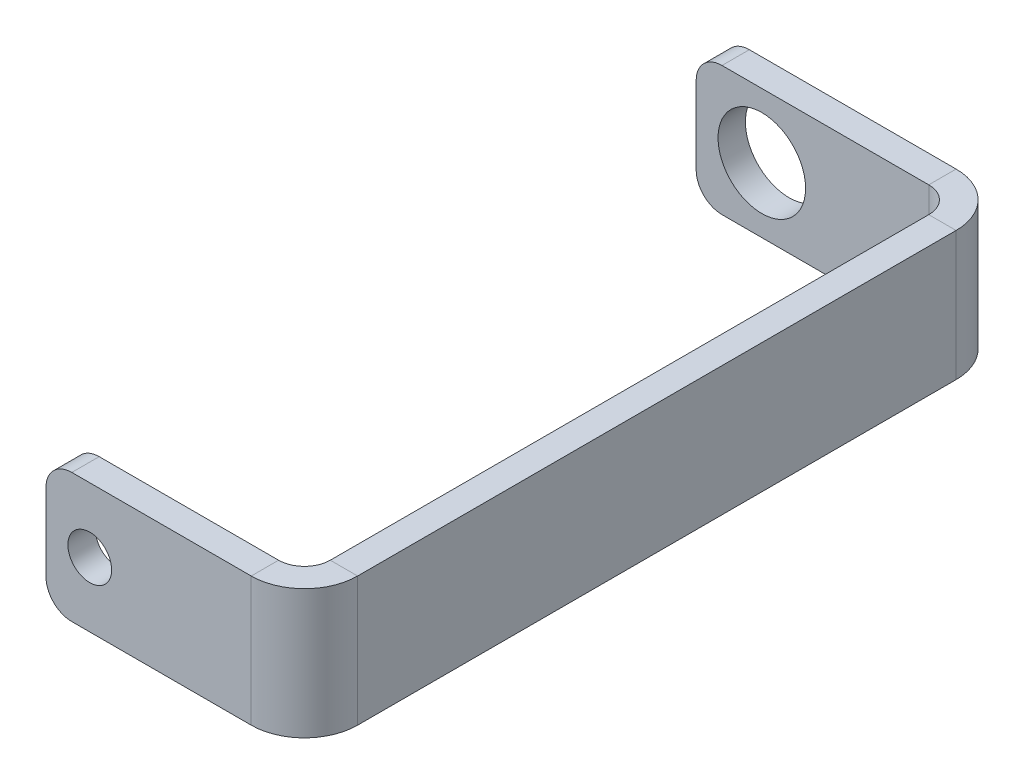
SolidWorks part; units mm, degrees
note: The reader was unsure of these and kept them because the rebuilt part matched: flange length of "Edge-Flange1", "Edge-Flange2".
material "Custom Plastic"
ref_plane "X-Y Datum" through (0, 0, 0) normal (0, 0, 1) x (1, 0, 0)
ref_plane "X-Z Datum" through (0, 0, 0) normal (0, 1, 0) x (1, 0, 0)
ref_plane "Y-Z Datum" through (0, 0, 0) normal (1, 0, 0) x (0, 0, -1)
sketch "Sketch1" plane through (0, 0, 0) normal (0, 0, 1) x (1, 0, 0)
  line L1 (-15, -7.5) -> (15, -7.5)
  line L2 (-15, -7.5) -> (-15, 7.5)
  line L3 (-15, 7.5) -> (15, 7.5)
  line L4 (15, -7.5) -> (15, 7.5)
  line L5 (-15, -7.5) -> (15, 7.5) construction
  line L6 (-15, 7.5) -> (15, -7.5) construction
  point P0 (0, 0)
  dimension "D1" = 30
  dimension "D2" = 15
base flange "Base-Flange1" sketch "Sketch1" thickness 3.175 reverse thickness direction no parameters "D1"=10
edge flange "Edge-Flange1" sketch "Sketch10" flange angle 90 flange length 78.652 flange position material outside bend radius 3 thickness 3.175 relief rectangular parameters "D6"=10
sketch "Sketch10" plane through (15, 0, 0) normal (-1, 0, 0) x (0, -1, 0)
  line L2 (-7.5, 0) -> (-7.5, 75.477)
  line L3 (-7.5, 75.477) -> (7.5, 75.477)
  line L4 (7.5, 75.477) -> (7.5, 0)
  line L5 (7.5, 0) -> (-7.5, 0) construction
  line L6 (7.5, 0) -> (-7.5, 0)
bend "EdgeBend1" bend radius 3 bend angle 90 parameters "D5"=1
edge flange "Edge-Flange2" sketch "Sketch13" flange angle 90 flange length 30 flange position material outside bend radius 3 thickness 3.175 relief rectangular parameters "D6"=10
sketch "Sketch13" plane through (15, 0, 75.477) normal (0, 0, -1) x (0, -1, 0)
  line L2 (-7.5, 0) -> (-7.5, 26.825)
  line L3 (-7.5, 26.825) -> (7.5, 26.825)
  line L4 (7.5, 26.825) -> (7.5, 0)
  line L5 (7.5, 0) -> (-7.5, 0) construction
  line L6 (7.5, 0) -> (-7.5, 0)
bend "EdgeBend2" bend radius 3 bend angle 90 parameters "D5"=2
sketch "Sketch14" plane through (0, 0, 0) normal (0, 0, 1) x (1, 0, 0)
  line L0 (-15, 0) -> (-7.38, 0)
  line L1 (-15, 7.5) -> (-15, -7.5) construction
  circle A0 centre (-7.38, 0) radius 5.08
  dimension "D1" = 10.16
  dimension "D2" = 7.62
extrude "Cut-Extrude1" cut sketch "Sketch14" against normal through all
sketch "Sketch15" plane through (0, 0, 78.652) normal (0, 0, 1) x (1, 0, 0)
  line L0 (-11.825, 0) -> (-6.745, 0)
  line L1 (-11.825, -7.5) -> (-11.825, 7.5) construction
  circle A0 centre (-6.745, 0) radius 2.54
  dimension "D1" = 5.08
extrude "Cut-Extrude2" cut sketch "Sketch15" against normal blind 10
fillet "Fillet1" radius 3 4 edges at (-11.825, 7.5, 77.0645) (-11.825, -7.5, 77.0645) (-15, 7.5, -1.5875) (-15, -7.5, -1.5875)
sketch "Bend-Lines1" [suppressed] plane through (0, 0, 0) normal (0, 1, 0) x (1, 0, 0)
sketch "Bounding-Box1" [suppressed] plane through (0, 0, 0) normal (0, 1, 0) x (1, 0, 0)
sheet metal parameters "Sheet-Metal1" thickness 3.175 parameters "D1"=10
flat pattern "Flat-Pattern1" [suppressed]
sketch "Bend-Lines2" plane through (0, 0, 0) normal (0, 1, 0) x (1, 0, 0)
sketch3d "Bounding-Box2" [suppressed]
  line L0 (-15, -7.5, 0) -> (15, -7.5, 0) construction
  line L1 (-15, 7.5, 0) -> (15, 7.5, 0) construction
  line L2 (-15, -7.5, 0) -> (-15, 7.5, 0) construction
  line L3 (15, -7.5, 0) -> (15, 7.5, 0) construction
sheet metal parameters "Sheet-Metal2" thickness 3.175 parameters "D1"=10
flat pattern "Flat-Pattern1"
sketch "Bend-Lines2" plane through (0, 0, 0) normal (0, 0, 1) x (1, 0, 0)
  line L0 (15.603, -7.5) -> (15.603, 7.5) construction
  line L1 (15.603, -7.5) -> (15.603, 7.5) construction
sketch3d "Bounding-Box2" [suppressed]
  line L0 (-15, -7.5, 0) -> (63.031, -7.5, 0) construction
  line L1 (-15, 7.5, 0) -> (63.031, 7.5, 0) construction
  line L2 (-15, -7.5, 0) -> (-15, 7.5, 0) construction
  line L3 (63.031, -7.5, 0) -> (63.031, 7.5, 0) construction
bend of the flat pattern "Flatten-<EdgeBend1>1"
sheet metal parameters "Sheet-Metal3" thickness 3.175 parameters "D1"=10
flat pattern "Flat-Pattern1"
sketch "Bend-Lines2" plane through (0, 0, 0) normal (0, 0, 1) x (1, 0, 0)
  line L0 (15.603, -7.5) -> (15.603, 7.5) construction
  line L1 (15.603, -7.5) -> (15.603, 7.5) construction
  line L2 (63.634, -7.5) -> (63.634, 7.5) construction
  line L3 (63.634, -7.5) -> (63.634, 7.5) construction
sketch3d "Bounding-Box2" [suppressed]
  line L0 (-15, -7.5, 0) -> (85.0621, -7.5, 0) construction
  line L1 (-15, 7.5, 0) -> (85.0621, 7.5, 0) construction
  line L2 (-15, -7.5, 0) -> (-15, 7.5, 0) construction
  line L3 (85.0621, -7.5, 0) -> (85.0621, 7.5, 0) construction
bend of the flat pattern "Flatten-<EdgeBend1>1"
bend of the flat pattern "Flatten-<EdgeBend2>1"
sheet metal parameters "Sheet-Metal4" thickness 3.175 parameters "D1"=10
flat pattern "Flat-Pattern1"
sketch "Bend-Lines2" plane through (0, 0, 0) normal (0, 0, 1) x (1, 0, 0)
  line L0 (13.103, -7.5) -> (13.103, 7.5) construction
  line L1 (13.103, -7.5) -> (13.103, 7.5) construction
  line L2 (88.086, -7.5) -> (88.086, 7.5) construction
  line L3 (88.086, -7.5) -> (88.086, 7.5) construction
sketch3d "Bounding-Box2" [suppressed]
  line L0 (-12.5, -7.5, 0) -> (115.5141, -7.5, 0) construction
  line L1 (-12.5, 7.5, 0) -> (115.5141, 7.5, 0) construction
  line L2 (-12.5, -7.5, 0) -> (-12.5, 7.5, 0) construction
  line L3 (115.5141, -7.5, 0) -> (115.5141, 7.5, 0) construction
bend of the flat pattern "Flatten-<EdgeBend1>1"
bend of the flat pattern "Flatten-<EdgeBend2>1"
sheet metal parameters "Sheet-Metal5" thickness 3.175 parameters "D1"=10
flat pattern "Flat-Pattern1"
sketch "Bend-Lines2" plane through (0, 0, 0) normal (0, 0, 1) x (1, 0, 0)
  line L0 (15.603, -7.5) -> (15.603, 7.5) construction
  line L1 (15.603, -7.5) -> (15.603, 7.5) construction
  line L2 (92.286, -7.5) -> (92.286, 7.5) construction
  line L3 (92.286, -7.5) -> (92.286, 7.5) construction
sketch3d "Bounding-Box2" [suppressed]
  line L0 (-15, -7.5, 0) -> (119.7141, -7.5, 0) construction
  line L1 (-15, 7.5, 0) -> (119.7141, 7.5, 0) construction
  line L2 (-15, -7.5, 0) -> (-15, 7.5, 0) construction
  line L3 (119.7141, -7.5, 0) -> (119.7141, 7.5, 0) construction
bend of the flat pattern "Flatten-<EdgeBend1>1"
bend of the flat pattern "Flatten-<EdgeBend2>1"
